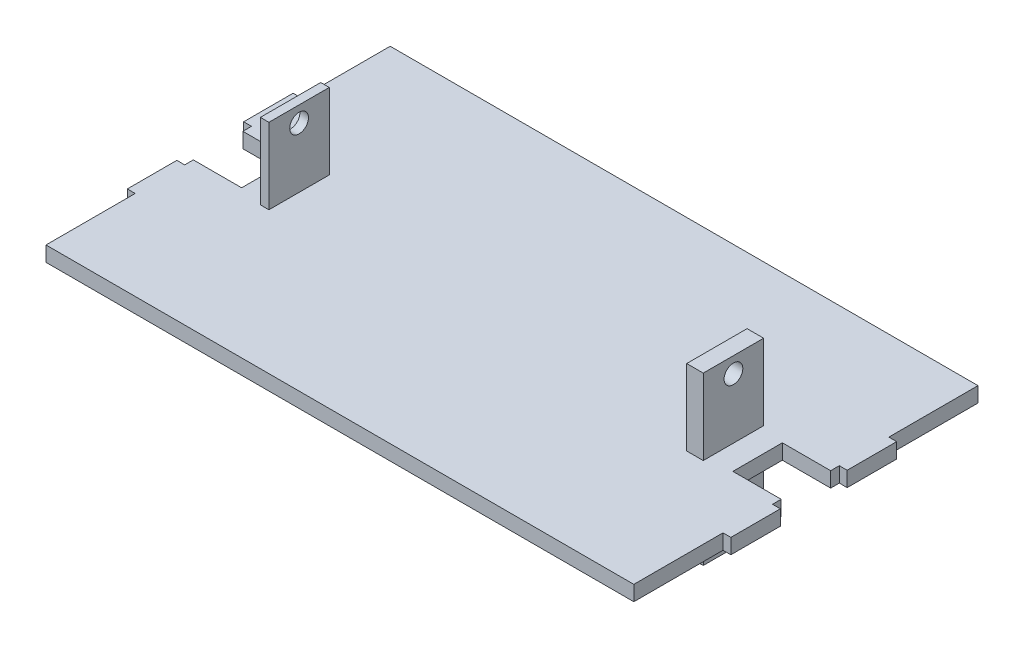
SolidWorks part; units mm, degrees
ref_plane "Front Plane" through (0, 0, 0) normal (0, 0, 1) x (1, 0, 0)
ref_plane "Top Plane" through (0, 0, 0) normal (0, 1, 0) x (1, 0, 0)
ref_plane "Right Plane" through (0, 0, 0) normal (1, 0, 0) x (0, 0, -1)
sketch "Sketch1" plane through (0, 0, 0) normal (0, 1, 0) x (1, 0, 0)
  line L0 (0, 72.39) -> (0, -72.39) construction
  line L1 (123.6345, -72.39) -> (-123.6345, -72.39)
  line L2 (123.6345, -72.39) -> (123.6345, -34.8747)
  line L3 (123.6345, 72.39) -> (-123.6345, 72.39)
  line L4 (-123.6345, -72.39) -> (-123.6345, -34.8747)
  line L5 (123.6345, -72.39) -> (-123.6345, 72.39) construction
  line L6 (123.6345, 72.39) -> (-123.6345, -72.39) construction
  line L7 (123.6345, 10.414) -> (103.3145, 10.414)
  line L9 (123.6345, -10.414) -> (103.3145, -10.414)
  line L10 (103.3145, 10.414) -> (103.3145, -10.414)
  line L13 (-123.6345, -10.414) -> (-103.3145, -10.414)
  line L14 (-103.3145, 10.414) -> (-103.3145, -10.414)
  line L15 (-123.6345, 10.414) -> (-103.3145, 10.414)
  line L17 (-127, 0) -> (127, 0) construction
  line L18 (-123.6345, 14.0467) -> (-126.9365, 14.0467)
  line L20 (-123.6345, 34.8747) -> (-126.9365, 34.8747)
  line L21 (-126.9365, 14.0467) -> (-126.9365, 34.8747)
  line L22 (-123.6345, -34.8747) -> (-126.9365, -34.8747)
  line L23 (-126.9365, -14.0467) -> (-126.9365, -34.8747)
  line L24 (-123.6345, -14.0467) -> (-126.9365, -14.0467)
  line L27 (123.6345, -14.0467) -> (126.9365, -14.0467)
  line L28 (126.9365, -14.0467) -> (126.9365, -34.8747)
  line L29 (123.6345, -34.8747) -> (126.9365, -34.8747)
  line L30 (123.6345, 34.8747) -> (126.9365, 34.8747)
  line L31 (126.9365, 14.0467) -> (126.9365, 34.8747)
  line L32 (123.6345, 14.0467) -> (126.9365, 14.0467)
  line L34 (-123.6345, 34.8747) -> (-123.6345, 72.39)
  line L35 (-123.6345, -14.0467) -> (-123.6345, -10.414)
  line L36 (123.6345, 34.8747) -> (123.6345, 72.39)
  line L37 (123.6345, -14.0467) -> (123.6345, -10.414)
  line L38 (-123.6345, 10.414) -> (-123.6345, 14.0467)
  line L39 (123.6345, 10.414) -> (123.6345, 14.0467)
  point P0 (0, 0)
  point P6 (127, 0)
  dimension "D1" = 247.269
  dimension "D2" = 144.78
  dimension "D3" = 20.828
  dimension "D5" = 3.302
  dimension "D6" = 20.828
  dimension "D4" = 20.32
extrude "Boss-Extrude1" add sketch "Sketch1" along normal mid plane 6.35
sketch "Sketch2" plane through (0, 0, 0) normal (0, 1, 0) x (1, 0, 0)
  line L0 (-103.3145, 10.414) -> (-103.3145, -10.414) construction
  line L1 (86.1922, -12.7) -> (93.1545, -12.7)
  line L2 (86.1922, -12.7) -> (86.1922, 12.7)
  line L3 (86.1922, 12.7) -> (93.1545, 12.7)
  line L4 (93.1545, -12.7) -> (93.1545, 12.7)
  line L5 (86.1922, -12.7) -> (93.1545, 12.7) construction
  line L6 (86.1922, 12.7) -> (93.1545, -12.7) construction
  line L9 (-89.5577, -12.7) -> (-89.5577, 12.7)
  line L10 (-89.5577, 12.7) -> (-93.1545, 12.7)
  line L11 (-93.1545, -12.7) -> (-93.1545, 12.7)
  line L12 (-89.5577, -12.7) -> (-93.1545, -12.7)
  line L13 (103.3145, -10.414) -> (103.3145, 10.414) construction
  point P0 (89.6734, 0)
  point P10 (103.3145, 0)
  dimension "D1" = 10.16
  dimension "D2" = 10.16
  dimension "D3" = 25.4
  dimension "D4" = 25.4
extrude "Boss-Extrude2" add sketch "Sketch2" along normal mid plane 70.104
sketch "Sketch3" plane through (-93.1545, 0, 0) normal (-1, 0, 0) x (0, 0, 1)
  circle A0 centre (0, 28.4406) radius 3.937
  circle A1 centre (0, -28.4406) radius 3.937
  dimension "D1" = 7.874
  dimension "D2" = 7.874
extrude "Cut-Extrude1" cut sketch "Sketch3" against normal through all both and the other way through all
equation "\"length\"=9.735"
equation "\"width\"= 5.7"
equation "\"height\"= 0.25"
equation "\"D1@Sketch1\"=\"length\""
equation "\"D2@Sketch1\"=\"width\""
equation "\"eyebolt width\"= 0.82"
equation "\"eyebolt length\"= 0.8"
equation "\"D3@Sketch1\"=\"eyebolt width\""
equation "\"D4@Sketch1\"=\"eyebolt length\""
equation "\"lead screw holder height\"= 2.76"
equation "\"lead screw diameter\"= 0.31"
equation "\"D1@Sketch3\"=\"lead screw diameter\""
equation "\"distance from holders to board\"=0.4"
equation "\"D2@Sketch3\"=\"lead screw diameter\""
